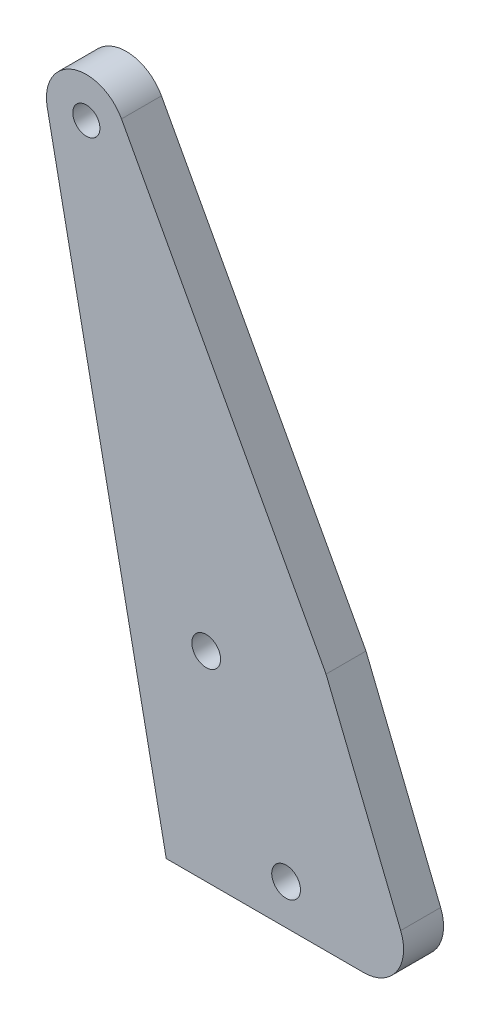
SolidWorks part; units mm, degrees
ref_plane "Front Plane" through (0, 0, 0) normal (0, 0, 1) x (1, 0, 0)
ref_plane "Top Plane" through (0, 0, 0) normal (0, 1, 0) x (1, 0, 0)
ref_plane "Right Plane" through (0, 0, 0) normal (1, 0, 0) x (0, 0, -1)
sketch "Sketch1" plane through (0, 0, 0) normal (0, 0, 1) x (1, 0, 0)
  line L1 (0, 0) -> (-25.4, 0)
  line L6 (-32.5135, 98.2688) -> (0, 38.1)
  line L7 (-44.3251, 93.9967) -> (-25.4, 0)
  line L9 (0, 38.1) -> (15.3934, 0)
  line L10 (15.3934, 0) -> (0, 0)
  line L11 (0, 38.1) -> (0, 0) construction
  line L12 (0, -22.9119) -> (0, 35.6119) construction
  arc A1 (-32.5135, 98.2688) -> (-44.3251, 93.9967) centre (-38.1, 95.25) ccw
  circle A2 centre (-6.35, 6.35) radius 2.286
  circle A3 centre (-19.05, 31.75) radius 2.286
  circle A4 centre (-38.1, 95.25) radius 2.159
  point P5 (-61.8336, 87.0538)
  dimension "D3" = 95.25
  dimension "D5" = 12.7
  dimension "D7" = 4.572
  dimension "D4" = 6.35
  dimension ".17" = 4.318
  dimension "D6" = 38.1
  dimension "D1" = 25.4
  dimension "D2" = 38.1
  dimension "D8" = 31.75
  dimension "D9" = 19.05
  dimension "D11" = 6.35
  dimension "D12" = 22
extrude "Boss-Extrude1" add sketch "Sketch1" against normal blind 6.35
fillet "Fillet1" radius 6.35 1 edges at (15.3934, 0, -3.175)
